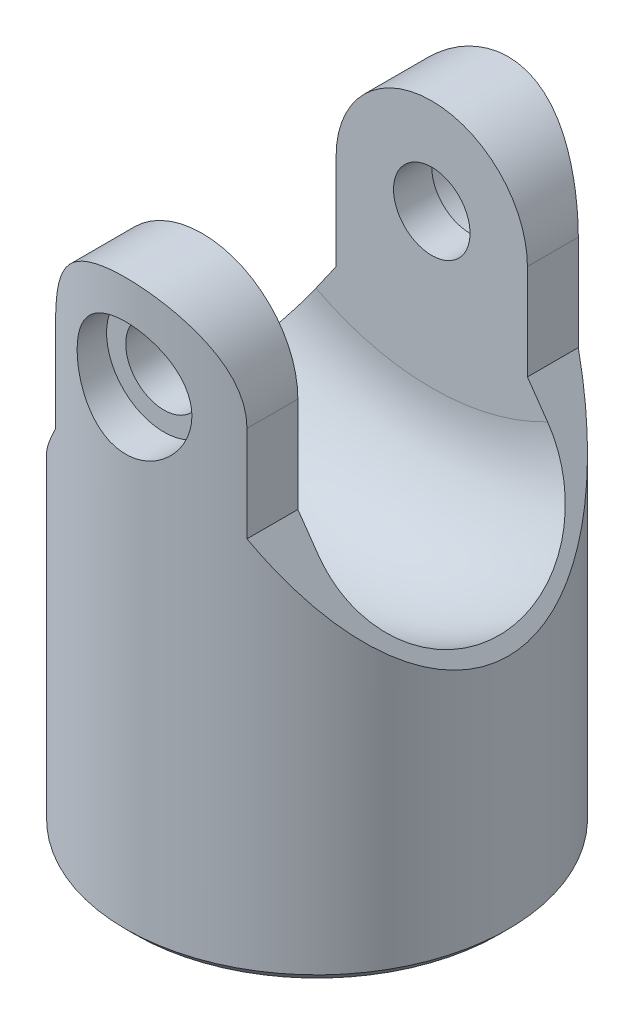
SolidWorks part; units mm, degrees
ref_plane "Alzado" through (0, 0, 0) normal (0, 0, 1) x (1, 0, 0)
ref_plane "Planta" through (0, 0, 0) normal (0, 1, 0) x (1, 0, 0)
ref_plane "Vista lateral" through (0, 0, 0) normal (1, 0, 0) x (0, 0, -1)
sketch "Croquis1" plane through (0, 0, 0) normal (0, 1, 0) x (1, 0, 0)
  circle A0 centre (0, 0) radius 20
  dimension "D1" = 40
extrude "Saliente-Extruir1" add sketch "Croquis1" along normal blind 110
sketch "Croquis2" plane through (0, 0, 0) normal (0, 0, 1) x (1, 0, 0)
  line L0 (-10, 100) -> (-10, 90)
  line L1 (-10, 90) -> (-20, 75.7185)
  line L2 (-20, 110) -> (-20, 0) construction
  line L3 (10, 100) -> (10, 90)
  line L4 (10, 90) -> (20, 75.7185)
  line L5 (20, 0) -> (20, 110) construction
  line L6 (-20, 75.7185) -> (-20, 110)
  line L7 (-20, 110) -> (20, 110)
  line L8 (20, 110) -> (20, 75.7185)
  arc A0 (10, 100) -> (-10, 100) centre (0, 100) ccw
  dimension "D1" = 10
  dimension "D2" = 10
  dimension "D3" = 145
  dimension "D4" = 145
extrude "Cortar-Extruir1" cut sketch "Croquis2" against normal blind 110 and the other way blind 110 contours A0 L7 L6 L1 L0 | A0 L3 L4 L8 L7 region at (14.8763, 96.9702, 0) region at (-14.8763, 96.9702, 0)
sketch "Croquis4" plane through (0, 0, 0) normal (0, 0, 1) x (1, 0, 0)
  circle A0 centre (0, 100) radius 4
  dimension "D1" = 8
extrude "Cortar-Extruir2" cut sketch "Croquis4" against normal blind 110 and the other way blind 110
sketch "Croquis3" plane through (0, 0, 0) normal (1, 0, 0) x (0, 0, -1)
  line L0 (20, 110) -> (-20, 110) construction
  line L1 (-12, 110) -> (12, 110)
  line L2 (-12, 110) -> (-12, 84)
  line L3 (-20, 104) -> (-20, 96) construction
  line L4 (12, 110) -> (12, 84)
  line L5 (0, 0) -> (0, 84) construction
  line L6 (-20, 0) -> (20, 0) construction
  line L7 (-20, 100) -> (19.5959, 100) construction
  line L8 (0, 84) -> (0, 110) construction
  arc A0 (-12, 84) -> (12, 84) centre (0, 84) ccw
  spline S1 degree 2 poles (-20, 104) (-19.2, 100) (-20, 96) knots 0 0 0 1 1 1 weights 0.016 0.02 0.024 construction
  spline S3 degree 2 poles (-20, 104) (-19.2, 100) (-20, 96) knots 0 0 0 1 1 1 weights 0.016 0.02 0.024 construction
  spline S4 degree 2 poles (20, 96) (19.2, 100) (20, 104) knots 0 0 0 1 1 1 weights 0.016 0.02 0.024 construction
  dimension "D2" = 16
  dimension "D3" = 12
  dimension "D1" = 24
revolve "Cortar-Revolución1" cut sketch "Croquis3" angle 360 about L1
ref_plane "Plano1" through (0, 0, 20) normal (0, 0, 1) x (1, 0, 0)
sketch "Croquis5" plane through (0, 0, 20) normal (0, 0, 1) x (1, 0, 0)
  circle A0 centre (0, 100) radius 6
  dimension "D1" = 12
extrude "Cortar-Extruir4" cut sketch "Croquis5" against normal blind 4
mirror "Simetría1" about plane through (0, 0, 0) normal (0, 0, 1) of "Cortar-Extruir4"
sketch "Croquis6" plane through (0, 0, 0) normal (0, 0, 1) x (1, 0, 0)
  line L0 (-20, 0) -> (20, 0) construction
  line L1 (-9, 0) -> (0, 0)
  line L2 (-9, 0) -> (-9, 30)
  line L3 (0, 70) -> (0, 0) construction
  line L4 (0, 70) -> (0, 0)
  line L5 (-9, 30) -> (-14, 30)
  line L8 (0, 70) -> (-14, 70)
  line L9 (-14, 30) -> (-14, 70)
  circle A0 centre (0, 100) radius 4 construction
  dimension "D1" = 28
  dimension "D2" = 40
  dimension "D3" = 30
  dimension "D5" = 9
revolve "Cortar-Revolución2" cut sketch "Croquis6" angle 360 about L3
sketch "Croquis10" plane through (0, 0, 0) normal (0, 0, 1) x (1, 0, 0)
  line L0 (-20, 0) -> (20, 0) construction
  line L1 (-20, 0) -> (20, 0)
  line L2 (-20, 0) -> (-20, 50)
  line L3 (-20, 50) -> (20, 50)
  line L4 (20, 0) -> (20, 50)
  line L5 (-20, 75.7185) -> (-20, 0) construction
  line L6 (20, 0) -> (20, 75.7185) construction
  circle A0 centre (0, 100) radius 4 construction
  dimension "D1" = 50
extrude "Cortar-Extruir5" cut sketch "Croquis10" against normal blind 40 and the other way blind 30
sketch "Croquis11" plane through (0, 70, 0) normal (0, -1, 0) x (1, 0, 0)
  circle A1 centre (0, 0) radius 14
  circle A2 centre (0, 0) radius 14
  dimension "D1" = 0
extrude "Saliente-Extruir2" add sketch "Croquis11" along normal up to surface (20 mm away) up to face at (0, 50, -14)
sketch "Croquis12" plane through (0, 50, 0) normal (0, -1, 0) x (1, 0, 0)
  circle A0 centre (0, 0) radius 10
  dimension "D1" = 20
extrude "Cortar-Extruir6" cut sketch "Croquis12" against normal blind 18
sketch "Croquis14" plane through (0, 50, 0) normal (0, -1, 0) x (1, 0, 0)
  line L0 (0, -10) -> (0, 0) construction
  line L1 (3, -9) -> (-3, -9)
  line L2 (3, -9) -> (3, -11)
  line L3 (3, -11) -> (-3, -11)
  line L4 (-3, -9) -> (-3, -11)
  line L5 (3, -9) -> (-3, -11) construction
  line L6 (3, -11) -> (-3, -9) construction
  circle A0 centre (0, 0) radius 10 construction
  circle A1 centre (0, 0) radius 10 construction
  point P0 (0, -10)
  point P10 (0, 0)
  point P13 (4.3511, -11.5473)
  dimension "D1" = 11
  dimension "D2" = 6
extrude "Cortar-Extruir7" cut sketch "Croquis14" against normal up to surface (18 mm away) up to face at (0, 68, -10)
ref_plane "Plano2" through (0, 0, -20) normal (0, 0, -1) x (-1, 0, 0)
sketch "Croquis16" plane through (0, 0, -20) normal (0, 0, -1) x (-1, 0, 0)
  line L0 (-20, 50) -> (20, 50) construction
  line L1 (0, 50) -> (0, 59) construction
  circle A0 centre (0, 59) radius 3
  dimension "D1" = 6
  dimension "D2" = 9
extrude "Cortar-Extruir8" cut sketch "Croquis16" against normal blind 9
chamfer "Chaflán1" distance 1 angle 45 1 edges at (0, 50, -20)
